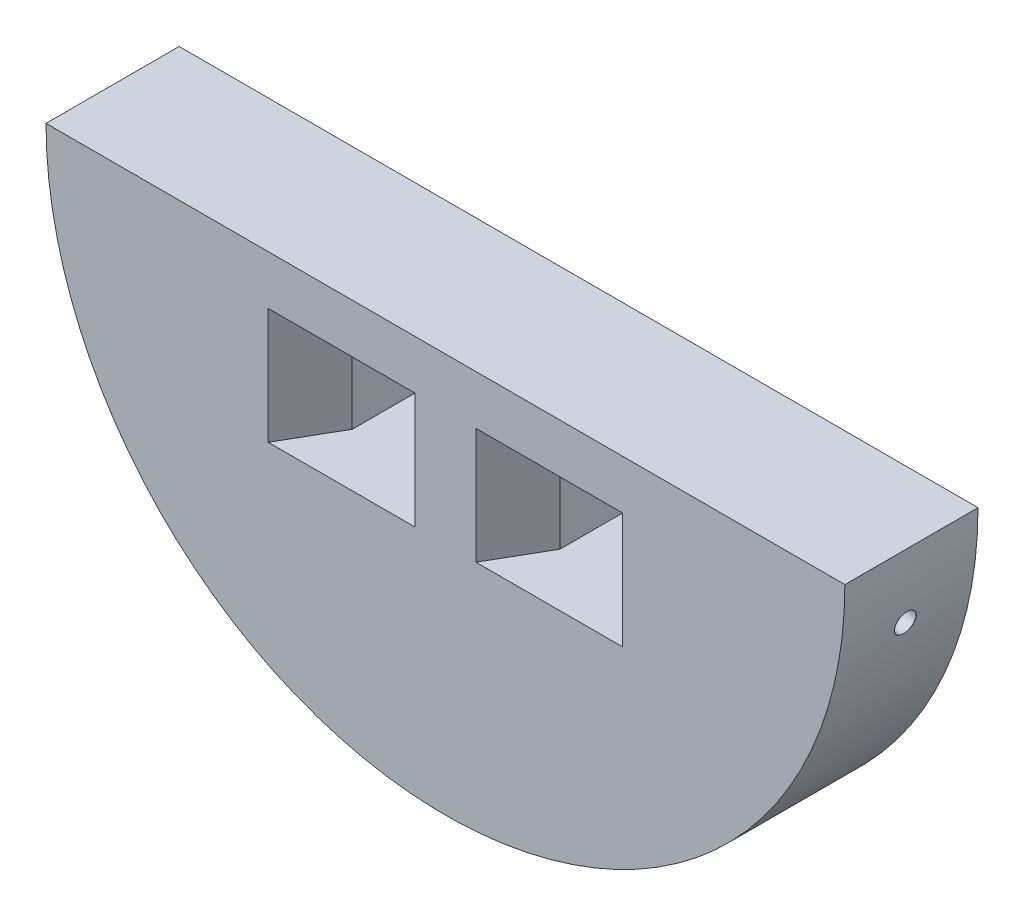
SolidWorks part; units mm, degrees
ref_plane "Front Plane" through (0, 0, 0) normal (0, 0, 1) x (1, 0, 0)
ref_plane "Top Plane" through (0, 0, 0) normal (0, 1, 0) x (1, 0, 0)
ref_plane "Right Plane" through (0, 0, 0) normal (1, 0, 0) x (0, 0, -1)
sketch "Sketch1" plane through (0, 0, 0) normal (0, 0, 1) x (1, 0, 0)
  line L0 (-150, 0) -> (0, 0)
  line L3 (-63.5, -31) -> (-47.5, -31)
  line L4 (-63.5, -31) -> (-63.5, -15)
  line L5 (-63.5, -15) -> (-47.5, -15)
  line L6 (-47.5, -31) -> (-47.5, -15)
  line L7 (-102.5, -31) -> (-86.5, -31)
  line L8 (-102.5, -31) -> (-102.5, -15)
  line L9 (-102.5, -15) -> (-86.5, -15)
  line L10 (-86.5, -31) -> (-86.5, -15)
  arc A1 (-150, 0) -> (0, 0) centre (-75, 0) ccw
  point P0 (-94.5, -15)
  point P13 (-55.5, -15)
  dimension "D1" = 19.5
  dimension "D7" = 75
  dimension "D2" = 15
  dimension "D3" = 19.5
  dimension "D4" = 16
extrude "Boss-Extrude1" add sketch "Sketch1" along normal blind 25
hole_wizard "Ø4.0mm Dowel Hole2" positions "3DSketch2" profile "Sketch4" hole size "Ø4.0" standard "ANSI Metric"
sketch3d "3DSketch2"
  line L2 (0, 0, 25) -> (0, 0, 0) construction
  line L4 (0, 0, 25) -> (0, 0, 0) construction
  line L5 (0, 0, 12.5) -> (-1.1394, -13.0236, 12.5) construction
  line L8 (-75, 0, 0) -> (-75, 0, 25) construction
  line L9 (0, 0, 0) -> (-150, 0, 0) construction
  line L10 (0, 0, 25) -> (-150, 0, 25) construction
  line L12 (-75, 0, 12.5) -> (-1.1394, -13.0236, 12.5) construction
  line L16 (-75, 0, 12.5) -> (0, 0, 12.5) construction
  point P0 (-1.1394, -13.0236, 12.5)
  point P16 (-1.1394, -13.0236, 12.5)
  point P23 (-1.1394, -13.0236, 12.5)
  point P25 (-1.1394, -13.0236, 12.5)
  dimension "D1" = 10
sketch "Sketch4" plane through (-1.1394, -13.0236, 12.5) normal (0, 0, 1) x (0.1736, 0.9848, 0)
  line L0 (0, 0) -> (0, 17.2017)
  line L1 (0, 17.2017) -> (2, 16)
  line L2 (2, 16) -> (2, 0.025)
  line L3 (2, 0.025) -> (2.025, 0)
  line L5 (2.025, 0) -> (0, 0)
  line L6 (-2, 0.025) -> (-2.025, 0) construction
  line L10 (0, 17.2017) -> (-2, 16) construction
  line L11 (0, -6.35) -> (0, 107.95) construction
  dimension "Hole Dia." = 4
  dimension "Hole Depth" = 16
  dimension "Near C'Sink Dia." = 4.05
  dimension "Near C'Sink Angle" = 90
  dimension "Drill Angle" = 118
pattern_circular "CirPattern1" count 5 over 160 about axis through (-75, 0, 0) along (0, 0, 1) of "Ø4.0mm Dowel Hole2" reverse direction yes
chamfer "Chamfer1" distance 15 angle 30 2 edges at (-94.5, -15, 0) (-55.5, -15, 0) first distance on face at (-94.5, -15, 12.5) first distance on face at (-55.5, -15, 12.5)
chamfer "Chamfer3" distance 10 angle 30 6 edges at (-102.5, -23, 25) (-94.5, -15, 25) (-86.5, -23, 25) (-47.5, -23, 25) (-55.5, -15, 25) (-63.5, -23, 25) first distance on face at (-102.5, -19.6679, 13) first distance on face at (-94.5, -15, 20) first distance on face at (-86.5, -19.6679, 13) first distance on face at (-47.5, -19.6679, 13) first distance on face at (-55.5, -15, 20) first distance on face at (-63.5, -19.6679, 13)
